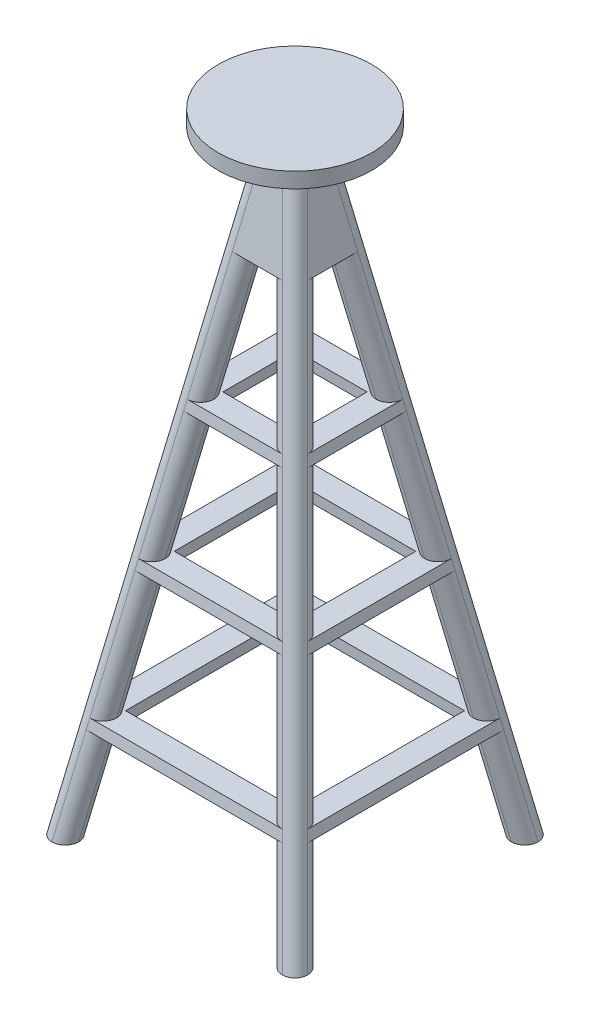
SolidWorks part; units mm, degrees
ref_plane "Alzado" through (0, 0, 0) normal (0, 0, 1) x (1, 0, 0)
ref_plane "Planta" through (0, 0, 0) normal (0, 1, 0) x (1, 0, 0)
ref_plane "Vista lateral" through (0, 0, 0) normal (1, 0, 0) x (0, 0, -1)
sketch "Croquis5" plane through (0, 0, 0) normal (0, 0, 1) x (1, 0, 0)
  line L1 (0, 0) -> (33.22, 0)
  line L2 (33.22, 0) -> (45.8065, 15)
  line L3 (45.8065, 15) -> (45.8065, 50)
  line L4 (45.8065, 50) -> (0, 50)
  line L6 (45.8065, 15) -> (45.8065, 0) construction
  line L7 (45.8065, 0) -> (33.22, 0) construction
  line L8 (0, 0) -> (0, 3)
  line L9 (0, 3) -> (31.8211, 3)
  line L10 (31.8211, 3) -> (42.8065, 16.0919)
  line L11 (42.8065, 16.0919) -> (42.8065, 47)
  line L12 (42.8065, 47) -> (0, 47)
  line L13 (0, 47) -> (0, 50)
  line L14 (0, 0) -> (0, 65.0712) construction
  dimension "D1" = 50
  dimension "D2" = 50
  dimension "D3" = 15
  dimension "D4" = 33.22
  dimension "D5" = 3
  dimension "D6" = 3
  dimension "D7" = 3
  dimension "D8" = 3
revolve "Revolución2" add sketch "Croquis5" angle 360 about L14
sketch "Croquis7" plane through (0, 50, 0) normal (0, 1, 0) x (1, 0, 0)
  line L5 (-25, 25) -> (25, 25)
  line L6 (-25, 25) -> (-25, -25)
  line L7 (-25, -25) -> (25, -25)
  line L8 (25, 25) -> (25, -25)
  line L9 (-25, 25) -> (25, -25) construction
  line L10 (-25, -25) -> (25, 25) construction
  point P0 (0, 0)
  dimension "D1" = 50
  dimension "D2" = 50
extrude "Saliente-Extruir3" add sketch "Croquis7" along normal blind 120
sketch "Croquis10" plane through (0, 0, 25) normal (0, 0, 1) x (1, 0, 0)
  line L0 (-25, 50) -> (-3.8408, 170)
  line L1 (-25, 170) -> (25, 170) construction
  line L2 (-3.8408, 170) -> (-25, 170)
  line L3 (-25, 170) -> (-25, 50)
  line L4 (25, 50) -> (25, 170)
  line L5 (25, 170) -> (3.8408, 170)
  line L6 (3.8408, 170) -> (25, 50)
  dimension "D1" = 10
  dimension "D2" = 10
extrude "Cortar-Extruir6" cut sketch "Croquis10" against normal through all
sketch "Croquis11" plane through (0, 0, 0) normal (1, 0, 0) x (0, 0, -1)
  line L0 (-25, 50) -> (-3.8408, 170)
  line L1 (25, 170) -> (-25, 170) construction
  line L2 (-3.8408, 170) -> (-25, 170)
  line L3 (-25, 170) -> (-25, 50)
  line L4 (25, 50) -> (25, 170)
  line L5 (25, 170) -> (3.8408, 170)
  line L6 (3.8408, 170) -> (25, 50)
  dimension "D1" = 10
  dimension "D2" = 10
extrude "Cortar-Extruir7" cut sketch "Croquis11" against normal through all both and the other way through all
sketch "Croquis12" plane through (0, 0, 0) normal (0, 0, 1) x (1, 0, 0)
  line L0 (-19.9229, 50) -> (19.9229, 50)
  line L1 (-25, 50) -> (25, 50) construction
  line L2 (19.9229, 50) -> (16.5727, 69)
  line L3 (2.2902, 150) -> (-2.2902, 150)
  line L4 (-2.2902, 150) -> (-6.6983, 125)
  line L5 (-6.6983, 125) -> (6.6983, 125)
  line L6 (-7.051, 123) -> (7.051, 123)
  line L7 (-25, 50) -> (-3.8408, 170) construction
  line L8 (3.8408, 170) -> (25, 50) construction
  line L9 (-11.4592, 98) -> (11.4592, 98)
  line L10 (-11.8118, 96) -> (11.8118, 96)
  line L11 (-16.5727, 69) -> (16.5727, 69)
  line L12 (-16.22, 71) -> (16.22, 71)
  line L13 (-7.051, 123) -> (-11.4592, 98)
  line L14 (6.6983, 125) -> (2.2902, 150)
  line L15 (11.4592, 98) -> (7.051, 123)
  line L16 (-11.8118, 96) -> (-16.22, 71)
  line L17 (-16.5727, 69) -> (-19.9229, 50)
  line L18 (16.22, 71) -> (11.8118, 96)
  dimension "D1" = 5
  dimension "D2" = 5
  dimension "D3" = 100
  dimension "D4" = 25
  dimension "D5" = 2
  dimension "D6" = 25
  dimension "D7" = 2
  dimension "D8" = 25
  dimension "D9" = 2
extrude "Cortar-Extruir8" cut sketch "Croquis12" against normal through all both and the other way through all
sketch "Croquis13" plane through (0, 0, 0) normal (1, 0, 0) x (0, 0, -1)
  line L0 (-19.9229, 50) -> (19.9229, 50)
  line L1 (-25, 50) -> (25, 50) construction
  line L2 (19.9229, 50) -> (16.5727, 69)
  line L3 (2.2902, 150) -> (-2.2902, 150)
  line L4 (-2.2902, 150) -> (-6.6983, 125)
  line L5 (-3.8408, 170) -> (-25, 50) construction
  line L6 (25, 50) -> (3.8408, 170) construction
  line L7 (-6.6983, 125) -> (6.6983, 125)
  line L8 (-7.051, 123) -> (7.051, 123)
  line L9 (-11.4592, 98) -> (11.4592, 98)
  line L10 (-11.8118, 96) -> (11.8118, 96)
  line L11 (-16.22, 71) -> (16.22, 71)
  line L12 (-16.5727, 69) -> (16.5727, 69)
  line L13 (-7.051, 123) -> (-11.4592, 98)
  line L14 (6.6983, 125) -> (2.2902, 150)
  line L15 (-11.8118, 96) -> (-16.22, 71)
  line L16 (11.4592, 98) -> (7.051, 123)
  line L17 (-16.5727, 69) -> (-19.9229, 50)
  line L18 (16.22, 71) -> (11.8118, 96)
  dimension "D1" = 5
  dimension "D2" = 5
  dimension "D3" = 100
  dimension "D4" = 2
  dimension "D5" = 2
  dimension "D6" = 2
  dimension "D7" = 25
  dimension "D8" = 25
  dimension "D9" = 25
extrude "Cortar-Extruir9" cut sketch "Croquis13" against normal through all both and the other way through all
sketch "Croquis15" plane through (0, 0, 0) normal (0, 0, 1) x (1, 0, 0)
  line L0 (45.8065, 50) -> (-45.8065, 50) construction
  line L1 (-53.4023, 20) -> (58.991, 20)
  line L2 (-53.4023, 20) -> (-53.4023, -24.7089)
  line L3 (-53.4023, -24.7089) -> (58.991, -24.7089)
  line L4 (58.991, 20) -> (58.991, -24.7089)
  dimension "D1" = 30
extrude "Cortar-Extruir10" cut sketch "Croquis15" against normal through all both and the other way through all
thread "Rosca2" pitch 2.5 method extrude profile "Perfil de rosca2" start angle 0, offset 0, length 17, pitch 2.5, diameter 85.613
ref_plane "Plano2" through (42.8065, 20, 0) normal (0, 0, 1) x (1, 0, 0)
sketch "Perfil de rosca2" plane through (42.8065, 20, 0) normal (0, 0, 1) x (1, 0, 0)
  line L0 (0, 0) -> (0, 2.5) construction
  line L11 (0, 0) -> (0, 2.1875)
  line L12 (0, 2.1875) -> (-1.3532, 1.4062)
  line L13 (-1.3532, 1.4062) -> (-1.3532, 0.7812)
  line L15 (-1.3532, 0.7812) -> (0, 0)
  line L17 (-1.3532, 1.0937) -> (0, 1.0937) construction
  point P2 (0, 0)
  dimension "Pitch" = 2.5
  dimension "Profile_Angle" = 60
  dimension "Profile_Land" = 0.625
  dimension "Profile_Height" = 1.3532
sketch "Croquis20" plane through (0, 0, 0) normal (0, 0, 1) x (1, 0, 0)
  line L0 (45.8065, 50) -> (-45.8065, 50) construction
  line L1 (-45.8065, 50) -> (45.8065, 50)
  line L2 (-45.8065, 50) -> (-45.8065, 20)
  line L3 (-45.8065, 20) -> (45.8065, 20)
  line L4 (45.8065, 50) -> (45.8065, 20)
extrude "Cortar-Extruir11" cut sketch "Croquis20" against normal through all both and the other way through all body kept at (-3.8408, 170, 3.8408)
sketch "Croquis21" plane through (0, 170, 0) normal (0, 1, 0) x (1, 0, 0)
  circle A0 centre (0, 0) radius 15
  dimension "D1" = 30
extrude "Saliente-Extruir4" add sketch "Croquis21" along normal blind 3
sketch "Croquis22" plane through (0, 69, 0) normal (0, -1, 0) x (1, 0, 0)
  line L1 (16.5727, -16.5727) -> (-16.5727, -16.5727)
  line L2 (16.5727, -16.5727) -> (16.5727, 16.5727)
  line L3 (16.5727, 16.5727) -> (-16.5727, 16.5727)
  line L4 (-16.5727, -16.5727) -> (-16.5727, 16.5727)
  line L5 (16.5727, -16.5727) -> (-16.5727, 16.5727) construction
  line L6 (16.5727, 16.5727) -> (-16.5727, -16.5727) construction
  point P0 (0, 0)
extrude "Cortar-Extruir12" cut sketch "Croquis22" against normal blind 2
sketch "Croquis23" plane through (0, 96, 0) normal (0, -1, 0) x (1, 0, 0)
  line L1 (11.8118, -11.8118) -> (-11.8118, -11.8118)
  line L2 (11.8118, -11.8118) -> (11.8118, 11.8118)
  line L3 (11.8118, 11.8118) -> (-11.8118, 11.8118)
  line L4 (-11.8118, -11.8118) -> (-11.8118, 11.8118)
  line L5 (11.8118, -11.8118) -> (-11.8118, 11.8118) construction
  line L6 (11.8118, 11.8118) -> (-11.8118, -11.8118) construction
  point P0 (0, 0)
extrude "Cortar-Extruir13" cut sketch "Croquis23" against normal blind 2
sketch "Croquis24" plane through (0, 123, 0) normal (0, -1, 0) x (1, 0, 0)
  line L1 (7.051, -7.051) -> (-7.051, -7.051)
  line L2 (7.051, -7.051) -> (7.051, 7.051)
  line L3 (7.051, 7.051) -> (-7.051, 7.051)
  line L4 (-7.051, -7.051) -> (-7.051, 7.051)
  line L5 (7.051, -7.051) -> (-7.051, 7.051) construction
  line L6 (7.051, 7.051) -> (-7.051, -7.051) construction
  point P0 (0, 0)
extrude "Cortar-Extruir14" cut sketch "Croquis24" against normal blind 2
fillet "Redondeo1" radius 2.5 52 edges at (-4.4943, 137.5, -9.5714) (-14.4204, 110, -14.4204) (-23.3249, 59.5, -18.2478) (18.2478, 59.5, -18.2478) (23.3249, 59.5, -18.2478) (14.4204, 110, -14.4204) (18.2478, 59.5, -23.3249) (18.2478, 59.5, 23.3249) (14.4204, 110, 14.4204) (9.5714, 137.5, 4.4943) (-4.4943, 137.5, 4.4943) (-4.4943, 137.5, 9.5714) (-9.5714, 137.5, 4.4943) (-14.4204, 110, 14.4204) (4.4943, 137.5, -4.4943) (9.2551, 110.5, -9.2551) (14.0159, 83.5, -14.0159) (9.5714, 137.5, -4.4943) (14.3322, 110.5, -9.2551) (19.093, 83.5, -14.0159) (-4.4943, 137.5, -4.4943) (-9.2551, 110.5, -9.2551) (-14.0159, 83.5, -14.0159) (-18.2478, 59.5, -18.2478) (-9.2551, 110.5, -14.3322) (-14.0159, 83.5, -19.093) (-18.2478, 59.5, -23.3249) (4.4943, 137.5, -9.5714) (9.2551, 110.5, -14.3322) (14.0159, 83.5, -19.093) (14.0159, 83.5, 19.093) (9.2551, 110.5, 14.3322) (4.4943, 137.5, 9.5714) (4.4943, 137.5, 4.4943) (9.2551, 110.5, 9.2551) (14.0159, 83.5, 14.0159) (14.3322, 110.5, 9.2551) (19.093, 83.5, 14.0159) (23.3249, 59.5, 18.2478) (18.2478, 59.5, 18.2478) (-9.2551, 110.5, 9.2551) (-14.0159, 83.5, 14.0159) (-14.3322, 110.5, 9.2551) (-19.093, 83.5, 14.0159) (-18.2478, 59.5, 18.2478) (-23.3249, 59.5, 18.2478) (-18.2478, 59.5, 23.3249) (-14.0159, 83.5, 19.093) (-9.2551, 110.5, 14.3322) (-19.093, 83.5, -14.0159) (-14.3322, 110.5, -9.2551) (-9.5714, 137.5, -4.4943)
